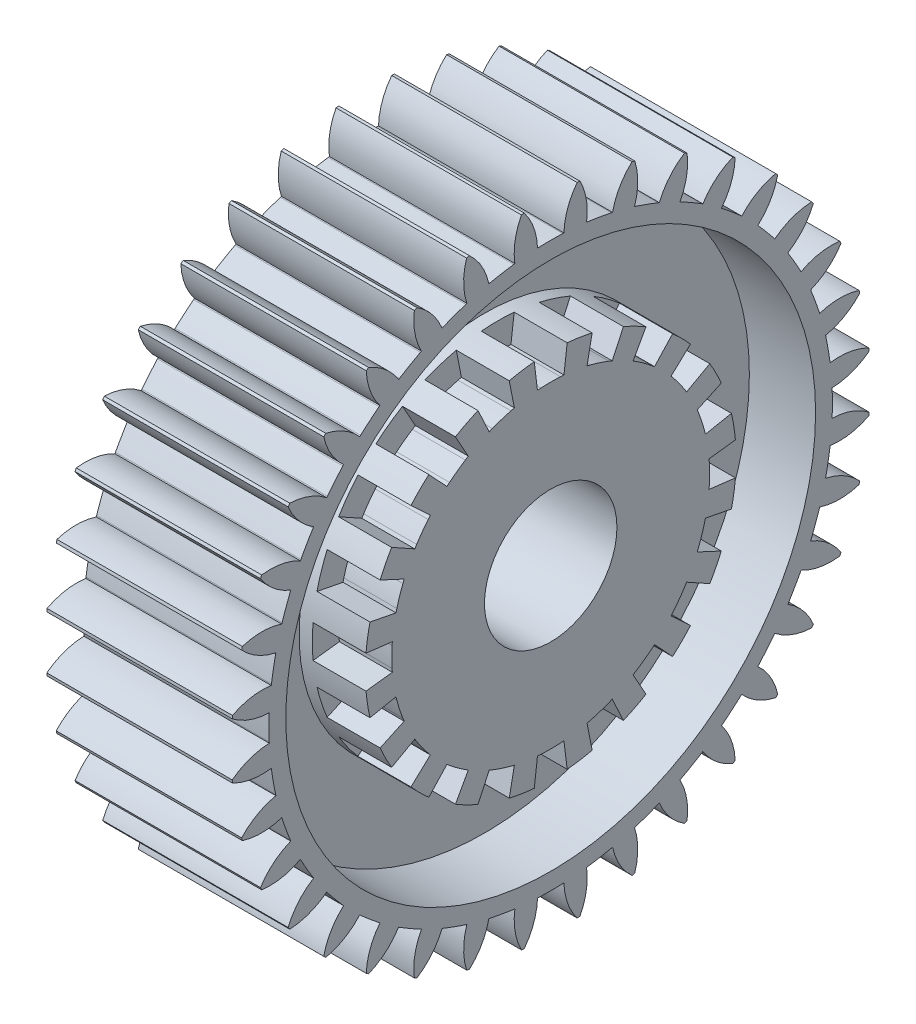
SolidWorks part; units mm, degrees
ref_plane "Front Plane" through (0, 0, 0) normal (0, 0, 1) x (1, 0, 0)
ref_plane "Top Plane" through (0, 0, 0) normal (0, 1, 0) x (1, 0, 0)
ref_plane "Right Plane" through (0, 0, 0) normal (1, 0, 0) x (0, 0, -1)
sketch "Sketch1" plane through (0, 0, 0) normal (1, 0, 0) x (0, 0, -1)
  circle A0 centre (0, 0) radius 120.65
  dimension "D1" = 241.3
extrude "Boss-Extrude1" add sketch "Sketch1" along normal mid plane 70
sketch "Sketch2" plane through (35, 0, 0) normal (1, 0, 0) x (0, 0, -1)
  circle A1 centre (0, 0) radius 25
  point P3 (0, 25)
  dimension "D1" = 50
extrude "Cut-Extrude1" cut sketch "Sketch2" against normal through all
sketch "Sketch3" plane through (35, 0, 0) normal (1, 0, 0) x (0, 0, -1)
  circle A0 centre (0, 0) radius 70
  circle A1 centre (0, 0) radius 100
  dimension "D1" = 140
  dimension "D2" = 200
extrude "Cut-Extrude2" cut sketch "Sketch3" against normal blind 25
sketch "Sketch4" plane through (35, 0, 0) normal (1, 0, 0) x (0, 0, -1)
  line L0 (0, 0) -> (0, 244.3511) construction
  line L1 (0, 106.4002) -> (-4.985, 106.2481)
  line L2 (0, 106.4002) -> (4.985, 106.2481)
  line L3 (-9.975, 120.2369) -> (0, 138.6182)
  line L4 (9.975, 120.2369) -> (0, 138.6182)
  circle A0 centre (0, 0) radius 114.3 construction
  circle A1 centre (0, 0) radius 106.365 construction
  arc A2 (-4.985, 106.2481) -> (-9.975, 120.2369) centre (-29.1557, 105.5105) ccw
  circle A3 centre (0, 0) radius 120.65 construction
  arc A4 (4.985, 106.2481) -> (9.975, 120.2369) centre (29.1557, 105.5105) cw
  dimension "D1" = 212.73
  dimension "D2" = 228.6
  dimension "D3" = 4.99
  dimension "D4" = 19.95
extrude "Cut-Extrude5" cut sketch "Sketch4" against normal through all
fillet "Fillet1" radius 150 1 edges at (0, 106.4002, 0)
pattern_circular "CirPattern1" count 36 over 360 about axis through (35, 0, 0) along (1, 0, 0) of "Fillet1", "Cut-Extrude5"
sketch "Sketch5" plane through (35, 0, 0) normal (1, 0, 0) x (0, 0, -1)
  line L0 (0, 0) -> (0, 102.3355) construction
  line L4 (-5, 59.7913) -> (-9.5713, 97.3774)
  line L5 (5, 59.7913) -> (9.5713, 97.3774)
  line L6 (-9.5713, 97.3774) -> (9.5713, 97.3774)
  line L8 (-5, 59.7913) -> (0, 60.0993)
  line L9 (0, 60.0993) -> (5, 59.7913)
  circle A0 centre (0, 0) radius 60 construction
  point P2 (0, 60.0993)
  dimension "D2" = 120
  dimension "D1" = 10
extrude "Cut-Extrude6" cut sketch "Sketch5" against normal blind 20
fillet "Fillet2" radius 60 1 edges at (25, 60.0993, 0)
pattern_circular "CirPattern2" count 20 over 360 about axis through (35, 0, 0) along (1, 0, 0) of "Fillet2", "Cut-Extrude6"
